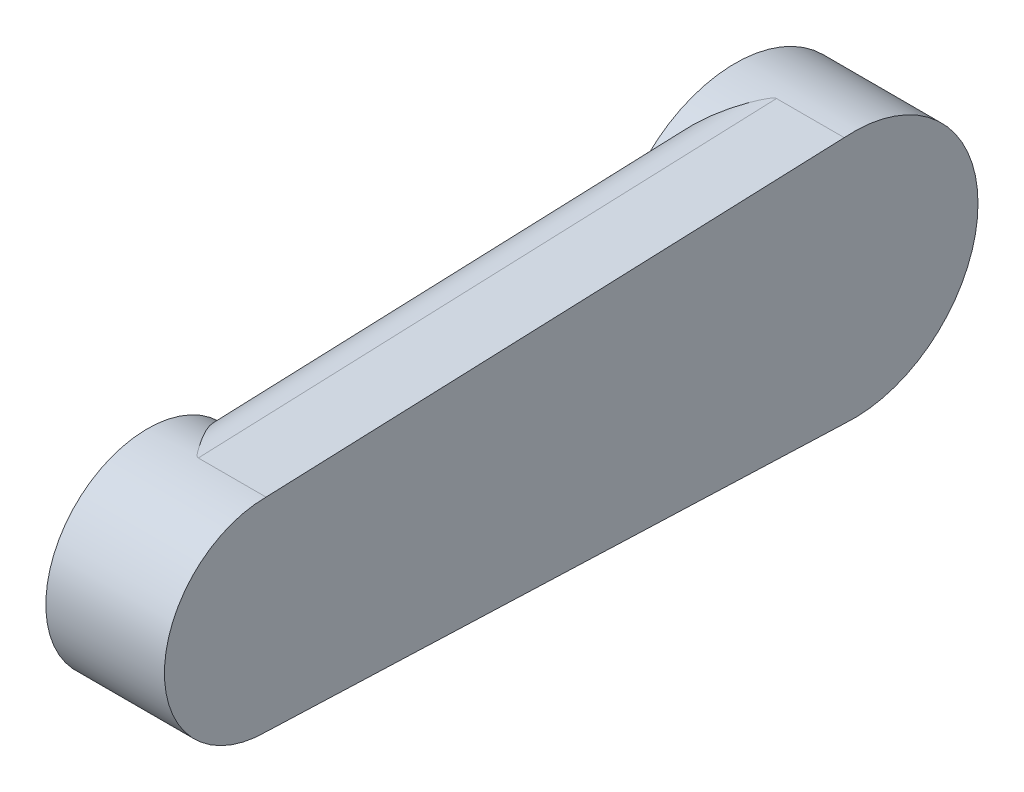
SolidWorks part; units mm, degrees
ref_plane "Front Plane" through (0, 0, 0) normal (0, 0, 1) x (1, 0, 0)
ref_plane "Top Plane" through (0, 0, 0) normal (0, 1, 0) x (1, 0, 0)
ref_plane "Right Plane" through (0, 0, 0) normal (1, 0, 0) x (0, 0, -1)
sketch "Sketch13" plane through (0, 0, 0) normal (1, 0, 0) x (0, 0, -1)
  line L0 (-5203.9758, 900) -> (-84.426, 1096.7553)
  line L1 (-5203.9758, -900) -> (-84.426, -1096.7553)
  arc A0 (-84.426, -1096.7553) -> (-84.426, 1096.7553) centre (0, 0) ccw
  arc A1 (-5203.9758, 900) -> (-5203.9758, -900) centre (-5203.9758, 0) ccw
extrude "Boss-Extrude11" add sketch "Sketch13" against normal blind 1050
fillet "Fillet3" radius 450 1 edges at (-1050, 998.3777, 2644.2009)
fillet "Fillet4" radius 450 1 edges at (-1050, -998.3777, 2644.2009)
sketch "Sketch14" plane through (-1050, 0, 0) normal (-1, 0, 0) x (0, 0, 1)
  line L0 (-96.738, 96.2772) -> (-96.738, 358.5674)
  line L1 (96.738, -358.5674) -> (-96.738, -358.5674)
  line L2 (96.738, -358.5674) -> (96.738, -96.2772)
  line L3 (96.738, 358.5674) -> (-96.738, 358.5674)
  line L4 (-96.738, -358.5674) -> (-96.738, -96.2772)
  line L5 (5264.6357, 55.8364) -> (5403.316, 55.8364)
  line L6 (5264.6357, -55.8364) -> (5403.316, -55.8364)
  line L7 (356.8591, 96.2772) -> (96.738, 96.2772)
  line L8 (356.8591, 96.2772) -> (356.8591, -96.2772)
  line L9 (356.8591, -96.2772) -> (96.738, -96.2772)
  line L10 (-356.8591, 96.2772) -> (-356.8591, -96.2772)
  line L13 (5264.6357, -216.5605) -> (5143.3159, -216.5605)
  line L14 (5264.6357, -216.5605) -> (5264.6357, -55.8364)
  line L15 (5264.6357, 216.5605) -> (5143.3159, 216.5605)
  line L16 (5143.3159, -216.5605) -> (5143.3159, -55.8364)
  line L19 (5004.6356, 55.8364) -> (5143.3159, 55.8364)
  line L20 (5004.6356, 55.8364) -> (5004.6356, -55.8364)
  line L21 (5004.6356, -55.8364) -> (5143.3159, -55.8364)
  line L22 (5403.316, 55.8364) -> (5403.316, -55.8364)
  line L29 (96.738, 96.2772) -> (96.738, 358.5674)
  line L30 (-96.738, -96.2772) -> (-356.8591, -96.2772)
  line L31 (-96.738, 96.2772) -> (-356.8591, 96.2772)
  line L32 (5143.3159, 55.8364) -> (5143.3159, 216.5605)
  line L33 (5264.6357, 55.8364) -> (5264.6357, 216.5605)
  circle A0 centre (0, 0) radius 500
  circle A1 centre (5203.9758, 0) radius 300
extrude "Boss-Extrude12" add sketch "Sketch14" along normal blind 141
